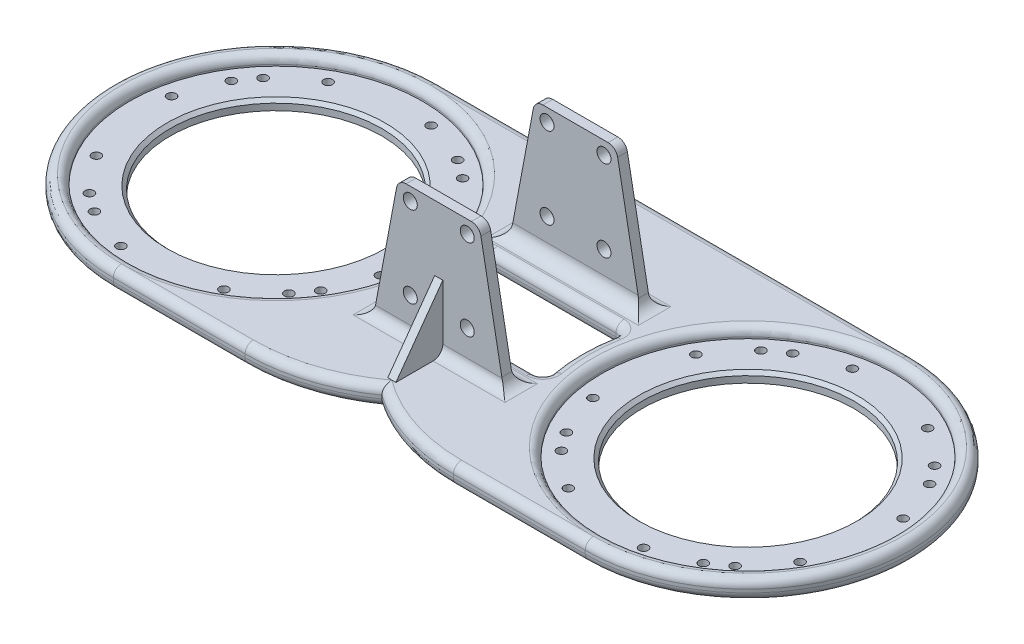
SolidWorks part; units mm, degrees
ref_plane "前视基准面" through (0, 0, 0) normal (0, 0, 1) x (1, 0, 0)
ref_plane "上视基准面" through (0, 0, 0) normal (0, 1, 0) x (1, 0, 0)
ref_plane "右视基准面" through (0, 0, 0) normal (1, 0, 0) x (0, 0, -1)
other "Configuration Table"
sketch "草图1" plane through (0, 0, 0) normal (0, 1, 0) x (1, 0, 0)
  line L0 (-145, 0) -> (145, 0) construction
  line L1 (-145, 100) -> (145, 100)
  line L2 (-145, -100) -> (145, -100)
  arc A0 (-145, 100) -> (-145, -100) centre (-145, 0) ccw
  arc A1 (145, -100) -> (145, 100) centre (145, 0) ccw
  point P3 (0, 0)
  dimension "D1" = 100
  dimension "D2" = 290
extrude "凸台-拉伸1" add sketch "草图1" along normal blind 6 and the other way blind 6
sketch "草图2" plane through (0, 0, 0) normal (0, 0, 1) x (1, 0, 0)
  line L0 (-145, 6) -> (-145, -6) construction
  line L1 (-145, -6) -> (-80, -6)
  line L2 (-145, -6) -> (145, -6) construction
  line L3 (-80, -6) -> (-80, 0)
  line L4 (-80, 0) -> (-55, 0)
  line L5 (-55, 0) -> (-55, 6)
  line L6 (-145, 6) -> (145, 6) construction
  line L7 (-55, 6) -> (-145, 6)
  line L8 (-145, 6) -> (-145, -6)
  dimension "D1" = 130
  dimension "D2" = 180
revolve "切除-旋转1" cut sketch "草图2" angle 360 about L0
sketch "草图3" plane through (0, 0, 0) normal (0, 1, 0) x (1, 0, 0)
  line L0 (-145, 0) -> (-129.4354, 79.7452) construction
  line L1 (-73.8216, 39.1816) -> (-145, 0) construction
  line L2 (-102.9484, 69.5214) -> (-145, 0) construction
  line L3 (-91.648, 61.2791) -> (-145, 0) construction
  line L4 (-145, 0) -> (-145, 81.25) construction
  circle A0 centre (-145, 0) radius 81.25 construction
  circle A1 centre (-102.9484, 69.5214) radius 2.75
  circle A2 centre (-91.648, 61.2791) radius 2.75
  circle A3 centre (-73.8216, 39.1816) radius 2.75
  circle A4 centre (-129.4354, 79.7452) radius 2.75
  circle A5 centre (-145, 0) radius 65 construction
  circle A18 centre (-75.4786, -42.0516) radius 2.75
  circle A19 centre (-83.7209, -53.352) radius 2.75
  circle A20 centre (-105.8184, -71.1784) radius 2.75
  circle A21 centre (-65.2548, -15.5646) radius 2.75
  circle A22 centre (-187.0516, -69.5214) radius 2.75
  circle A23 centre (-198.352, -61.2791) radius 2.75
  circle A24 centre (-216.1784, -39.1816) radius 2.75
  circle A25 centre (-160.5646, -79.7452) radius 2.75
  circle A26 centre (-214.5214, 42.0516) radius 2.75
  circle A27 centre (-206.2791, 53.352) radius 2.75
  circle A28 centre (-184.1816, 71.1784) radius 2.75
  circle A29 centre (-224.7452, 15.5646) radius 2.75
  point P41 (-145, 0)
  dimension "D1" = 162.5
  dimension "D2" = 5.5
  dimension "D3" = 50.124
  dimension "D4" = 20.124
  dimension "D5" = 20.124
  dimension "D6" = 11.044
  dimension "D7" = 4
extrude "切除-拉伸1" cut sketch "草图3" against normal up to next
mirror "镜向1" about plane through (0, 0, 0) normal (1, 0, 0) of "切除-拉伸1", "切除-旋转1"
sketch "草图4" plane through (0, 6, 0) normal (0, 1, 0) x (1, 0, 0)
  line L0 (0, -80) -> (0, -100) construction
  line L1 (-145, -100) -> (145, -100) construction
  line L2 (-64, -100) -> (64, -100)
  arc A0 (0, -80) -> (64, -100) centre (64, 12.4) ccw
  arc A1 (0, -80) -> (-64, -100) centre (-64, 12.4) cw
  dimension "D1" = 20
  dimension "D2" = 64
extrude "切除-拉伸2" cut sketch "草图4" against normal up to next
fillet "圆角1" radius 5 7 edges at (0, -6, -100) (245, -6, 0) (-104.5, -6, 100) (104.5, -6, 100) (-245, -6, 0) (30.4739, -6, 94.8835) (-30.4739, -6, 94.8835)
fillet "圆角2" radius 5 9 edges at (0, 6, -100) (245, 6, 0) (104.5, 6, 100) (-104.5, 6, 100) (-245, 6, 0) (-145, 6, 90) (145, 6, 90) (30.4739, 6, 94.8835) (-30.4739, 6, 94.8835)
chamfer "倒角1" distance 2 angle 45 2 edges at (-145, 0, 65) (145, 0, 65)
sketch "草图5" plane through (0, 0, 0) normal (0, 0, 1) x (1, 0, 0)
  line L0 (-40, 6) -> (40, 6)
  line L1 (64, 6) -> (0, 6) construction
  line L2 (40, 6) -> (25, 86)
  line L3 (25, 86) -> (-25, 86)
  line L4 (0, 86) -> (0, 6) construction
  line L5 (-40, 6) -> (-25, 86)
  dimension "D1" = 80
  dimension "D2" = 50
  dimension "D3" = 80
extrude "凸台-拉伸2" add sketch "草图5" along normal mid plane 90
sketch "草图6" plane through (0, 0, 0) normal (1, 0, 0) x (0, 0, -1)
  line L0 (0, 86) -> (0, 6) construction
  line L1 (-45, 6) -> (45, 6) construction
  line L8 (-45, 86) -> (45, 86) construction
  line L16 (45, 6) -> (45, 86) construction
  line L17 (-39, 6) -> (39, 6)
  line L18 (-39, 6) -> (-39, 86)
  line L19 (-39, 86) -> (39, 86)
  line L20 (39, 6) -> (39, 86)
  line L21 (-39, 6) -> (39, 86) construction
  line L22 (-39, 86) -> (39, 6) construction
  point P4 (0, 0)
  point P5 (0, 6)
  point P6 (0, 46)
  dimension "D1" = 6
extrude "切除-拉伸3" cut sketch "草图6" against normal mid plane 150
sketch "草图7" plane through (0, 0, 0) normal (1, 0, 0) x (0, 0, -1)
  line L0 (39, 6) -> (45, 6) construction
  line L1 (39, 6) -> (45, 6) construction
  line L2 (45, 6) -> (95, 6) construction
  line L3 (70, 6) -> (45, 46)
  line L4 (45, 6) -> (45, 86) construction
rib "筋2" sketch "草图7" sketch "草图7" thickness 5 extrusion direction parallel to sketch draft on no parameters "D1"=5
sketch "草图8" plane through (0, 0, 0) normal (1, 0, 0) x (0, 0, -1)
  line L0 (-73.8482, 6) -> (-45, 6) construction
  line L1 (-73.8482, 6) -> (-45, 46)
  line L2 (-45, 6) -> (-45, 86) construction
rib "筋3" sketch "草图8" sketch "草图8" thickness 5 extrusion direction parallel to sketch draft on no parameters "D1"=5
sketch "草图9" plane through (0, 0, 45) normal (0, 0, 1) x (1, 0, 0)
  line L0 (25, 86) -> (-25, 86) construction
  line L1 (-17.5, 78) -> (17.5, 78) construction
  line L2 (-17.5, 78) -> (-17.5, 28) construction
  line L3 (-17.5, 28) -> (17.5, 28) construction
  line L4 (17.5, 78) -> (17.5, 28) construction
  line L5 (0, 86) -> (0, 6) construction
  circle A0 centre (-17.5, 78) radius 4.3
  circle A1 centre (17.5, 78) radius 4.3
  circle A2 centre (17.5, 28) radius 4.3
  circle A3 centre (-17.5, 28) radius 4.3
  point P9 (0, 78)
  dimension "D2" = 8.6
  dimension "D1" = 8
  dimension "D3" = 35
  dimension "D4" = 50
extrude "切除-拉伸4" cut sketch "草图9" against normal up to surface (90 mm away) up to face at (0, 36, -45)
fillet "圆角4" radius 8 6 edges at (40, 6, -42) (40, 6, 42) (-40, 6, -42) (-40, 6, 42) (0, 6, 39) (0, 6, -39)
fillet "圆角5" radius 6 4 edges at (24.5697, 6, 45) (-24.5697, 6, 45) (24.5697, 6, -45) (-24.5697, 6, -45)
fillet "圆角6" radius 6 4 edges at (-25, 86, 42) (25, 86, 42) (25, 86, -42) (-25, 86, -42)
sketch "草图10" plane through (0, 6, 0) normal (0, 1, 0) x (1, 0, 0)
  line L0 (-45.08, 25) -> (45.08, 25)
  line L1 (46.6394, 31) -> (-46.6394, 31) construction
  line L2 (45.08, -25) -> (-45.08, -25)
  line L3 (-42, 0) -> (42, 0) construction
  arc A0 (45.08, 25) -> (45.08, -25) centre (145, 0) ccw
  arc A1 (-45.08, -25) -> (-45.08, 25) centre (-145, 0) ccw
  circle A2 centre (145, 0) radius 95 construction
  dimension "D1" = 8
  dimension "D2" = 6
extrude "切除-拉伸5" cut sketch "草图10" against normal up to next
fillet "圆角7" radius 5 12 edges at (0, 6, 25) (0, -6, 25) (-45.08, 0, 25) (-42, 6, 0) (-42, -6, 0) (42, 6, 0) (45.08, 0, 25) (42, -6, 0) (-45.08, 0, -25) (0, 6, -25) (45.08, 0, -25) (0, -6, -25)
